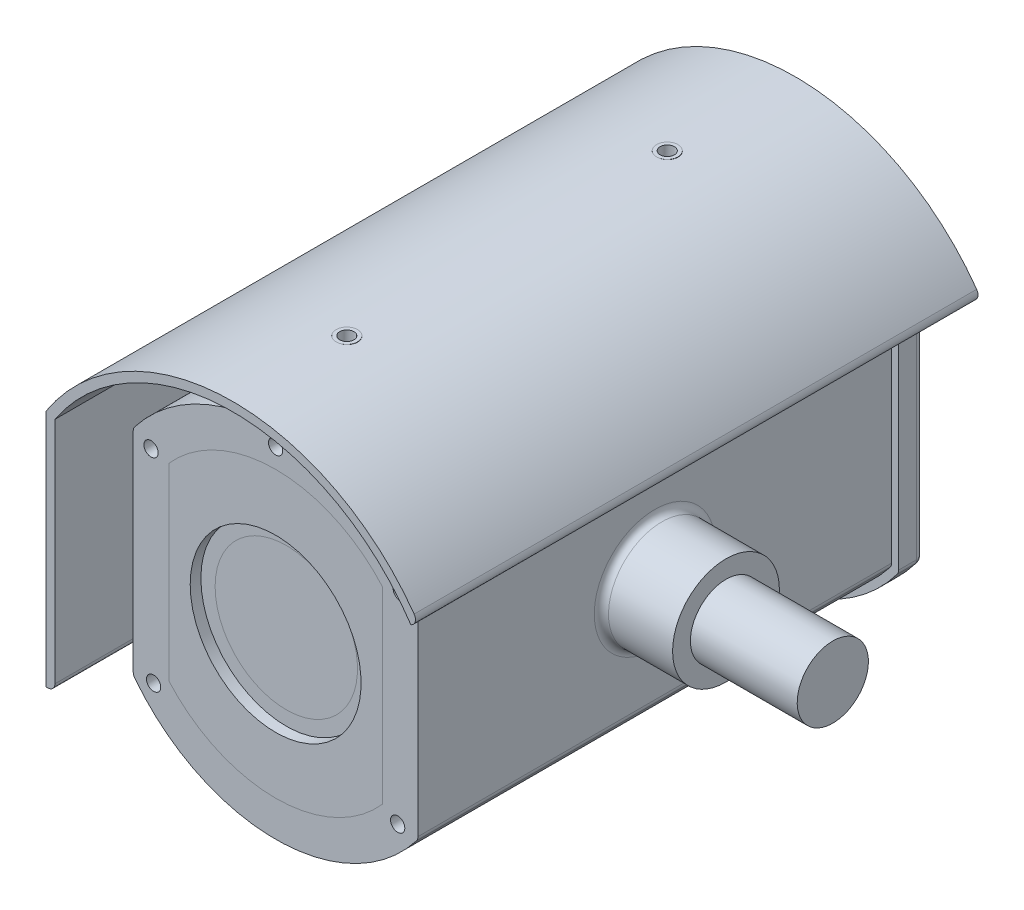
SolidWorks part; units mm, degrees
ref_plane "Front Plane" through (0, 0, 0) normal (0, 0, 1) x (1, 0, 0)
ref_plane "Top Plane" through (0, 0, 0) normal (0, 1, 0) x (1, 0, 0)
ref_plane "Right Plane" through (0, 0, 0) normal (1, 0, 0) x (0, 0, -1)
sketch "Sketch1" plane through (0, 0, 0) normal (0, 0, 1) x (1, 0, 0)
  line L2 (-40, -30) -> (-40, 30)
  line L3 (40, -30) -> (40, 30)
  line L5 (40, 0) -> (-40, 0) construction
  arc A0 (40, 30) -> (-40, 30) centre (0, 0) ccw
  arc A1 (40, -30) -> (-40, -30) centre (0, 0) cw
  point P18 (40, 0)
  point P19 (-40, 0)
  dimension "D1" = 60
  dimension "D2" = 80
extrude "Boss-Extrude1" add sketch "Sketch1" along normal blind 140
sketch "Sketch2" plane through (0, 0, 140) normal (0, 0, 1) x (1, 0, 0)
  line L4 (-30, 26.4575) -> (-30, -26.4575)
  line L5 (30, -26.4575) -> (30, 26.4575)
  line L6 (-30, 26.4575) -> (-30, -26.4575)
  line L7 (30, -26.4575) -> (30, 26.4575)
  arc A4 (30, 26.4575) -> (-30, 26.4575) centre (0, 0) ccw
  arc A5 (-30, -26.4575) -> (30, -26.4575) centre (0, 0) ccw
  arc A6 (30, 26.4575) -> (-30, 26.4575) centre (0, 0) ccw
  arc A7 (-30, -26.4575) -> (30, -26.4575) centre (0, 0) ccw
  dimension "D1" = 10
extrude "Cut-Extrude1" cut sketch "Sketch2" against normal blind 7
sketch "Sketch3" plane through (0, 0, 140) normal (0, 0, 1) x (1, 0, 0)
  line L2 (52.5, -33.1662) -> (52.5, 33.9116)
  line L3 (-50, 33.1662) -> (-52.0833, 34.5482)
  line L4 (-50, 33.1662) -> (-50, -33.1662)
  line L5 (50, -33.1662) -> (50, 33.1662)
  line L6 (52.5, -33.1662) -> (50, -33.1662)
  line L7 (50, -33.1662) -> (50, 33.1662)
  arc A2 (52.5, 33.9116) -> (-52.0833, 34.5482) centre (0, 0) ccw
  arc A4 (50, 33.1662) -> (-50, 33.1662) centre (0, 0) ccw
  arc A5 (-50, -33.1662) -> (50, -33.1662) centre (0, 0) ccw
  arc A6 (50, 33.1662) -> (-50, 33.1662) centre (0, 0) ccw
  dimension "D1" = 10
  dimension "D2" = 2.5
extrude "Boss-Extrude2" add sketch "Sketch3" along normal blind 12 and the other way blind 146 separate body
sketch "Sketch4" plane through (0, 0, 133) normal (0, 0, 1) x (1, 0, 0)
  circle A0 centre (0, 0) radius 20
  circle A1 centre (0, 0) radius 24
  dimension "D1" = 40
  dimension "D3" = 4
extrude "Boss-Extrude3" add sketch "Sketch4" along normal blind 4
sketch "Sketch5" plane through (0, 0, 133) normal (0, 0, 1) x (1, 0, 0)
  circle A1 centre (0, 0) radius 20
  circle A2 centre (0, 0) radius 20
  dimension "D1" = 0
extrude "Cut-Extrude2" cut sketch "Sketch5" against normal blind 7
sketch "Sketch6" plane through (0, 0, 126) normal (0, 0, 1) x (1, 0, 0)
  circle A0 centre (0, 0) radius 11
  dimension "D1" = 22
extrude "Cut-Extrude3" cut sketch "Sketch6" against normal blind 1
dome "Dome1" faces to dome 1 distance 5 reverse direction no elliptical dome no face at (11, 0, 125) parameters "D1"=5
sketch "Sketch7" plane through (52.5, 0, 0) normal (1, 0, 0) x (0, 0, -1)
  circle A0 centre (-120, 0) radius 3
  circle A1 centre (-30, 0) radius 3
  dimension "D3" = 6
  dimension "D1" = 90
  dimension "D2" = 30
extrude "Boss-Extrude4" add sketch "Sketch7" against normal up to surface (12.5 mm away) up to face at (40, 0, 70)
sketch "Sketch8" plane through (52.5, 0, 0) normal (1, 0, 0) x (0, 0, -1)
  circle A6 centre (-120, 0) radius 2
  circle A8 centre (-30, 0) radius 2
  dimension "D1" = 4
extrude "Cut-Extrude4" cut sketch "Sketch8" against normal blind 17
ref_plane "Plane1" through (0, 62.5, 0) normal (0, 1, 0) x (-1, 0, 0)
sketch "Sketch9" plane through (0, 62.5, 0) normal (0, 1, 0) x (-1, 0, 0)
  line L0 (-52.5, 120) -> (0, 120) construction
  line L1 (-52.5, 123) -> (-52.5, 117) construction
  circle A0 centre (0, 120) radius 3
  circle A1 centre (0, 30) radius 3
  dimension "D2" = 6
  dimension "D1" = 90
extrude "Boss-Extrude5" add sketch "Sketch9" against normal up to surface (12.5 mm away) up to face at (0, 40, 70)
sketch "Sketch10" plane through (0, 62.5, 0) normal (0, 1, 0) x (1, 0, 0)
  circle A0 centre (0, -30) radius 2
  circle A1 centre (0, -120) radius 2
  arc A2 (0, -123) -> (0, -117) centre (0, -120) ccw construction
  dimension "D1" = 4
extrude "Cut-Extrude5" cut sketch "Sketch10" against normal blind 17
sketch "Sketch11" plane through (0, 0, 0) normal (0, 0, -1) x (-1, 0, 0)
  line L4 (-42, 30.6594) -> (-42, -30.6594)
  line L5 (42, -30.6594) -> (42, 30.6594)
  line L6 (-42, 30.6594) -> (-42, -30.6594)
  line L7 (42, -30.6594) -> (42, 30.6594)
  line L8 (-40, 30) -> (-40, -30)
  line L9 (40, -30) -> (40, 30)
  line L10 (-40, 30) -> (-40, -30)
  line L11 (40, -30) -> (40, 30)
  arc A4 (42, 30.6594) -> (-42, 30.6594) centre (0, 0) ccw
  arc A5 (-42, -30.6594) -> (42, -30.6594) centre (0, 0) ccw
  arc A6 (42, 30.6594) -> (-42, 30.6594) centre (0, 0) ccw
  arc A7 (-42, -30.6594) -> (42, -30.6594) centre (0, 0) ccw
  arc A8 (40, 30) -> (-40, 30) centre (0, 0) ccw
  arc A9 (-40, -30) -> (40, -30) centre (0, 0) ccw
  arc A10 (40, 30) -> (-40, 30) centre (0, 0) ccw
  arc A11 (-40, -30) -> (40, -30) centre (0, 0) ccw
  dimension "D1" = 2
  dimension "D2" = 0
extrude "Boss-Extrude6" add sketch "Sketch11" against normal blind 7
sketch "Sketch12" plane through (0, 0, 0) normal (0, 0, -1) x (-1, 0, 0)
  line L0 (-35, -2.5) -> (35, -2.5)
  line L1 (-35, -6) -> (35, -6)
  line L2 (-35, -12) -> (35, -12)
  line L3 (-35, -8.5) -> (35, -8.5)
  line L4 (-35, 0) -> (35, 0)
  line L5 (-35, 3.5) -> (35, 3.5)
  line L6 (-35, 28.2843) -> (-35, -28.2843)
  line L7 (35, -28.2843) -> (35, 28.2843)
  line L8 (-35, 28.2843) -> (-35, -28.2843)
  line L9 (35, -28.2843) -> (35, 28.2843)
  line L10 (-35, 6) -> (35, 6)
  line L11 (-35, 9.5) -> (35, 9.5)
  line L12 (-35, 12) -> (35, 12)
  line L13 (-35, 15.5) -> (35, 15.5)
  line L14 (-35, 18) -> (35, 18)
  line L15 (-35, 21.5) -> (35, 21.5)
  line L16 (-35, 24) -> (35, 24)
  line L17 (-35, 27.5) -> (35, 27.5)
  line L18 (-33.541, 30) -> (33.541, 30)
  line L19 (-30.0458, 33.5) -> (30.0458, 33.5)
  line L20 (-27, 36) -> (27, 36)
  line L21 (-21.5581, 39.5) -> (21.5581, 39.5)
  line L22 (-16.1555, 42) -> (16.1555, 42)
  line L23 (-35, -18) -> (35, -18)
  line L24 (-35, -14.5) -> (35, -14.5)
  line L25 (-35, -24) -> (35, -24)
  line L26 (-35, -20.5) -> (35, -20.5)
  line L27 (-33.541, -30) -> (33.541, -30)
  line L28 (-35, -26.5) -> (35, -26.5)
  line L29 (-35, 45.5) -> (35, 45.5) [skipped]
  line L30 (-27, -36) -> (27, -36)
  line L31 (-31.1247, -32.5) -> (31.1247, -32.5)
  line L32 (-16.1555, -42) -> (16.1555, -42)
  line L33 (-23.297, -38.5) -> (23.297, -38.5)
  arc A7 (35, 28.2843) -> (-35, 28.2843) centre (0, 0) ccw
  arc A8 (-35, -28.2843) -> (35, -28.2843) centre (0, 0) ccw
  arc A9 (35, 28.2843) -> (-35, 28.2843) centre (0, 0) ccw
  arc A10 (-35, -28.2843) -> (35, -28.2843) centre (0, 0) ccw
  dimension "D2" = 3.5
  dimension "D4" = 2.5
  dimension "D5" = 3.5
  dimension "D1" = 7
  dimension "D3" = 8
  dimension "D6" = 7
extrude "Cut-Extrude6" cut sketch "Sketch12" against normal blind 5 contours L22 A9 | L20 A9 L21 | L18 A9 L19 | L17 L8 L16 L9 | L15 L8 L14 L9 | L13 L8 L12 L9 | L11 L8 L10 L9 | L4 L9 L5 L8 | L1 L9 L0 L8 | L2 L9 L3 L8 | L24 L8 L23 L9 | L26 L8 L25 L9 | L8 A10 L27 L9 L28 | L31 A10 L30 | L33 A10 L32 region at (0, -4.25, 0) region at (0, 1.75, 0) region at (0, -10.25, 0) region at (0, 7.75, 0) region at (0, -16.25, 0) region at (0, 13.75, 0) region at (0, -22.25, 0) region at (0, 19.75, 0) region at (0, -28.238, 0) region at (0, 25.75, 0) region at (0, -34.2088, 0) region at (0, 31.718, 0) region at (0, -40.1467, 0) region at (0, 37.6852, 0) region at (0, 43.2035, 0)
ref_plane "Plane2" through (-101.0147, 0, 0) normal (1, 0, 0) x (0, 0, -1)
sketch "Sketch14" plane through (0, 0, 137) normal (0, 0, 1) x (1, 0, 0)
  circle A0 centre (0, 0) radius 20 construction
  circle A1 centre (0, 0) radius 20
extrude "Boss-Extrude7" add sketch "Sketch14" against normal blind 2 separate body
sketch "Sketch15" plane through (0, 0, 140) normal (0, 0, 1) x (1, 0, 0)
  line L0 (-30, 26.4575) -> (-30, -26.4575) construction
  line L1 (30, -26.4575) -> (30, 26.4575) construction
  line L2 (-30, 26.4575) -> (-30, -26.4575)
  line L3 (30, -26.4575) -> (30, 26.4575)
  arc A0 (30, 26.4575) -> (-30, 26.4575) centre (0, 0) ccw construction
  arc A1 (30, 26.4575) -> (-30, 26.4575) centre (0, 0) ccw
  arc A2 (-30, -26.4575) -> (30, -26.4575) centre (0, 0) ccw construction
  circle A3 centre (0, 0) radius 24 construction
  arc A4 (-30, -26.4575) -> (30, -26.4575) centre (0, 0) ccw
  circle A5 centre (0, 0) radius 24
extrude "Boss-Extrude8" add sketch "Sketch15" against normal blind 5 separate body
sketch "Sketch16" plane through (0, 0, 140) normal (0, 0, 1) x (1, 0, 0)
  line L0 (2, 45.5) -> (-2, 45.5) construction
  circle A0 centre (35, 27.5) radius 2
  circle A1 centre (-35, 27.5) radius 2
  circle A2 centre (0, 45.5) radius 2
  circle A3 centre (34.2812, -29.1513) radius 2
  arc A4 (33.541, -30) -> (35, -28.2843) centre (0, 0) ccw construction
  circle A5 centre (-34.2812, -29.1513) radius 2
  arc A6 (-35, -28.2843) -> (-33.541, -30) centre (0, 0) ccw construction
  dimension "D1" = 4
extrude "Cut-Extrude8" cut sketch "Sketch16" against normal blind 5
mirror "Mirror2" about plane through (-101.0147, 0, 0) normal (1, 0, 0) of bodies 115 114 116 112
sketch "Sketch13" plane through (0, 0, 0) normal (0, 0, 1) x (1, 0, 0)
  circle A0 centre (0, 0) radius 124.2871
extrude "Cut-Extrude7" cut sketch "Sketch13" along normal through all and the other way through all
sketch "Sketch17" plane through (-162.0295, 0, 0) normal (1, 0, 0) x (0, 0, -1)
  line L0 (-73.5, -30) -> (-73.5, 0) construction
  line L1 (-140, -30) -> (-7, -30) construction
  circle A0 centre (-73.5, 0) radius 10
  dimension "D1" = 20
extrude "Boss-Extrude9" add sketch "Sketch17" along normal blind 50
sketch "Sketch18" plane through (-162.0295, 0, 0) normal (1, 0, 0) x (0, 0, -1)
  circle A0 centre (-73.5, 0) radius 10 construction
  circle A1 centre (-73.5, 0) radius 10
  circle A2 centre (-73.5, 0) radius 15
  dimension "D1" = 5
extrude "Boss-Extrude10" add sketch "Sketch18" along normal blind 20
fillet "Fillet1" radius 2 23 edges at (-242.0295, -3, 30) (-252.0295, -3, 120) (-252.0295, -3, 30) (-242.0295, -3, 120) (-202.7153, 59.9961, 117.0794) (-202.7153, 59.9961, 27.0794) (-201.3455, 49.9953, 27.079) (-149.9462, 34.5482, 73) (-202.0295, 52, 0) (-160.0295, 0, 0) (-202.0295, -52, 0) (-244.0295, 0, 0) (-244.0295, 30.6594, 3.5) (-244.0295, -30.6594, 3.5) (-242.0295, 30, 73.5) (-242.0295, -30, 73.5) (-252.0295, -33.1662, 73) (-160.0295, 30.6594, 3.5) (-160.0295, -30.6594, 3.5) (-162.0295, 30, 73.5) (-162.0295, -30, 73.5) (-201.3455, 49.9953, 117.079) (-162.0295, -15, 73.5)
